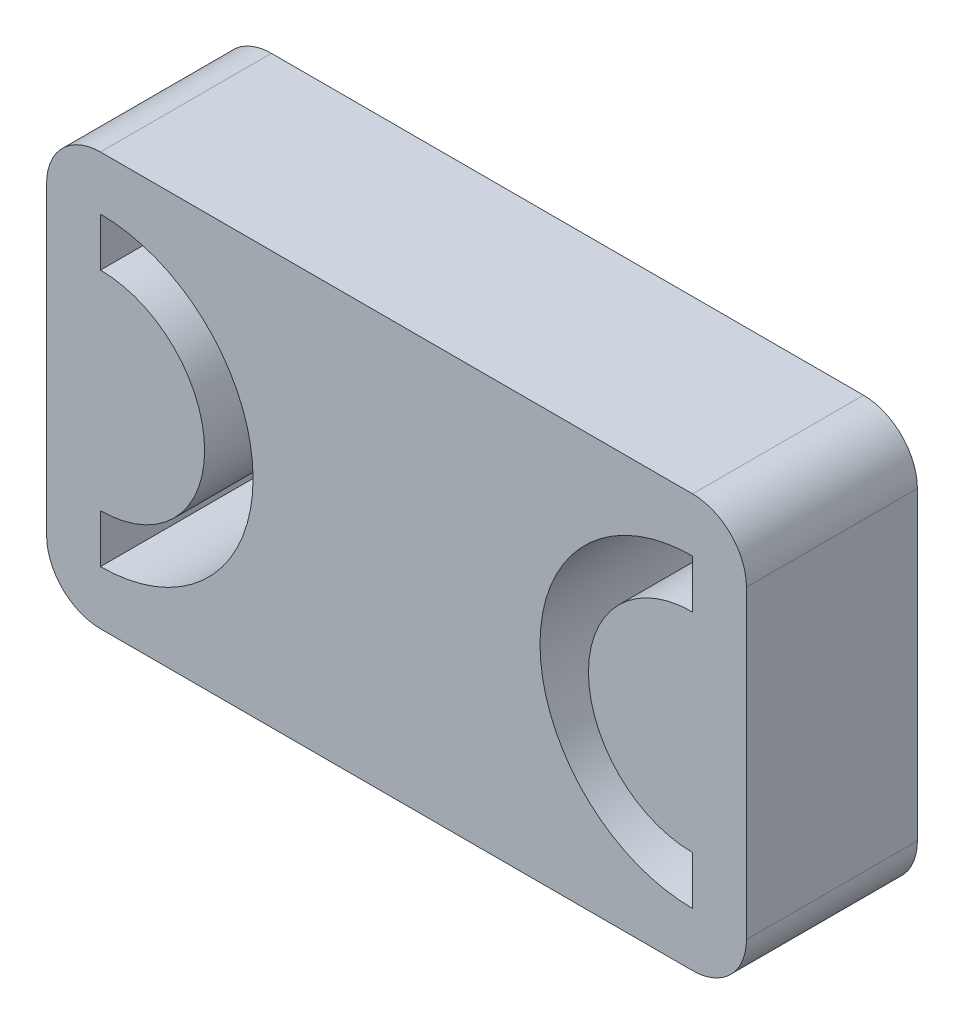
SolidWorks part; units mm, degrees
material "Copper"
ref_plane "Front Plane" through (0, 0, 0) normal (0, 0, 1) x (1, 0, 0)
ref_plane "Top Plane" through (0, 0, 0) normal (0, 1, 0) x (1, 0, 0)
ref_plane "Right Plane" through (0, 0, 0) normal (1, 0, 0) x (0, 0, -1)
sketch "Sketch1" plane through (0, 0, 0) normal (0, 0, 1) x (1, 0, 0)
  line L0 (0, 0) -> (0, 30) construction
  line L3 (-5.5, 2.835) -> (-5.5, 1.935)
  line L4 (-5.5, -1.935) -> (-5.5, -2.835)
  line L5 (5.5, -1.935) -> (5.5, -2.835)
  line L6 (5.5, 2.835) -> (5.5, 1.935)
  line L7 (-6.5, -1.935) -> (-6.5, -3.7023)
  line L8 (-6.5, 3.7023) -> (-6.5, 1.935)
  line L9 (-6.5, 1.935) -> (-6.5, -1.935)
  line L10 (6.5, 3.7023) -> (6.5, 1.935)
  line L11 (6.5, -1.935) -> (6.5, -3.7023)
  line L12 (6.5, 1.935) -> (6.5, -1.935)
  line L13 (-5.5, 3.835) -> (5.5, 3.835)
  line L14 (0, 0) -> (-1.665, 0) construction
  line L15 (-5.5, -3.835) -> (5.5, -3.835)
  arc A0 (-5.5, -2.835) -> (-5.5, 2.835) centre (-5.5, 0) ccw
  arc A1 (5.5, 2.835) -> (5.5, -2.835) centre (5.5, 0) ccw
  arc A2 (-5.5, -1.935) -> (-5.5, 1.935) centre (-5.5, 0) ccw
  arc A3 (5.5, 1.935) -> (5.5, -1.935) centre (5.5, 0) ccw
  arc A4 (-6.5, -3.7023) -> (-5.5, -3.835) centre (-5.5, 0) ccw
  arc A5 (6.5, -3.7023) -> (5.5, -3.835) centre (5.5, 0) cw
  arc A6 (-5.5, 3.835) -> (-6.5, 3.7023) centre (-5.5, 0) ccw
  arc A7 (5.5, 3.835) -> (6.5, 3.7023) centre (5.5, 0) cw
  arc A8 (-6.5, -3.7023) -> (-6.5, 3.7023) centre (-5.5, 0) ccw construction
  dimension "D2" = 5.67
  dimension "D3" = 11
  dimension "D4" = 3.87
  dimension "D1" = 30
  dimension "D5" = 1
extrude "Boss-Extrude2" add sketch "Sketch1" along normal mid plane 3.175
fillet "Fillet2" radius 1 4 edges at (6.5, -3.7023, 0) (-6.5, -3.7023, 0) (6.5, 3.7023, 0) (-6.5, 3.7023, 0)
